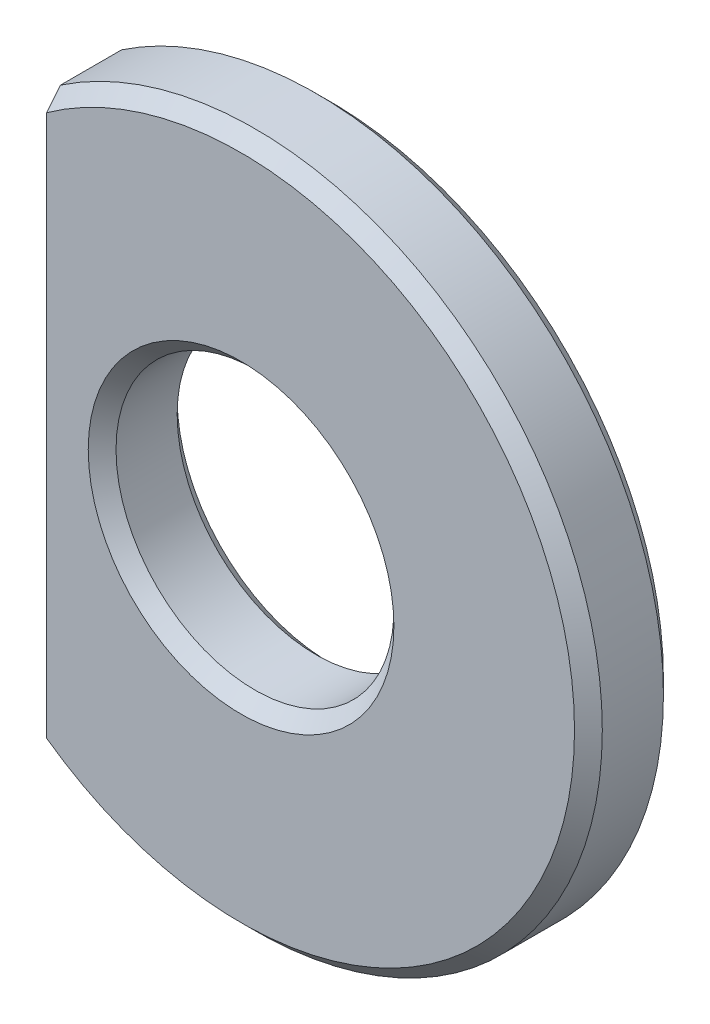
SolidWorks part; units mm, degrees
ref_plane "前视基准面" through (0, 0, 0) normal (0, 0, 1) x (1, 0, 0)
ref_plane "上视基准面" through (0, 0, 0) normal (0, 1, 0) x (1, 0, 0)
ref_plane "右视基准面" through (0, 0, 0) normal (1, 0, 0) x (0, 0, -1)
sketch "草图1" plane through (0, 0, 0) normal (0, 1, 0) x (1, 0, 0)
  line L0 (5, 2.7) -> (5, 0.5)
  line L1 (5, 0.5) -> (5.5, 0)
  line L2 (5.5, 0) -> (12, 0)
  line L3 (12, 0) -> (12.5, 0.5)
  line L4 (12.5, 0.5) -> (12.5, 2.7)
  line L5 (12.5, 2.7) -> (12, 3.2)
  line L6 (12, 3.2) -> (5.5, 3.2)
  line L7 (5.5, 3.2) -> (5, 2.7)
  line L8 (0, -3) -> (0, 3) construction
revolve "旋转1" add sketch "草图1" angle 360 about L8 reverse direction yes
sketch "草图2" plane through (0, 0, 0) normal (0, 0, 1) x (1, 0, 0)
  line L0 (-32, -12.5) -> (-7, -12.5)
  line L1 (-7, -12.5) -> (-7, 12.5)
  line L2 (-7, 12.5) -> (-32, 12.5)
  line L3 (-32, 12.5) -> (-32, -12.5)
extrude "切除-拉伸1" cut sketch "草图2" against normal blind 3.2
ref_plane "基准面4" through (0, 0, -3.2) normal (0, 0, 1) x (1, 0, 0)
ref_plane "spring XY" through (0, 0, 0) normal (0, 0, 1) x (1, 0, 0)
ref_plane "spring XZ" through (0, 0, 0) normal (0, -1, 0) x (-1, 0, 0)
ref_plane "spring YZ" through (0, 0, 0) normal (1, 0, 0) x (0, 0, -1)
ref_axis "spring X" through (-80.9, 0, 0) along (1, 0, 0)
ref_axis "spring Y" through (0, -50, 0) along (0, 1, 0)
ref_axis "spring Z" through (0, 0, 80.9) along (0, 0, -1)
sketch3d "spring"
  point P0 (0, 0, 0)
ref_plane "to_bolt XY" through (0, 0, -3.2) normal (0, 0, 1) x (1, 0, 0)
ref_plane "to_bolt XZ" through (0, 0, 0) normal (0, -1, 0) x (-1, 0, 0)
ref_plane "to_bolt YZ" through (0, 0, 0) normal (1, 0, 0) x (0, 0, -1)
ref_axis "to_bolt X" through (-80.9, 0, -3.2) along (1, 0, 0)
ref_axis "to_bolt Y" through (0, -50, -3.2) along (0, 1, 0)
ref_axis "to_bolt Z" through (0, 0, 80.9) along (0, 0, -1)
sketch3d "to_bolt"
  point P0 (0, 0, -3.2)
